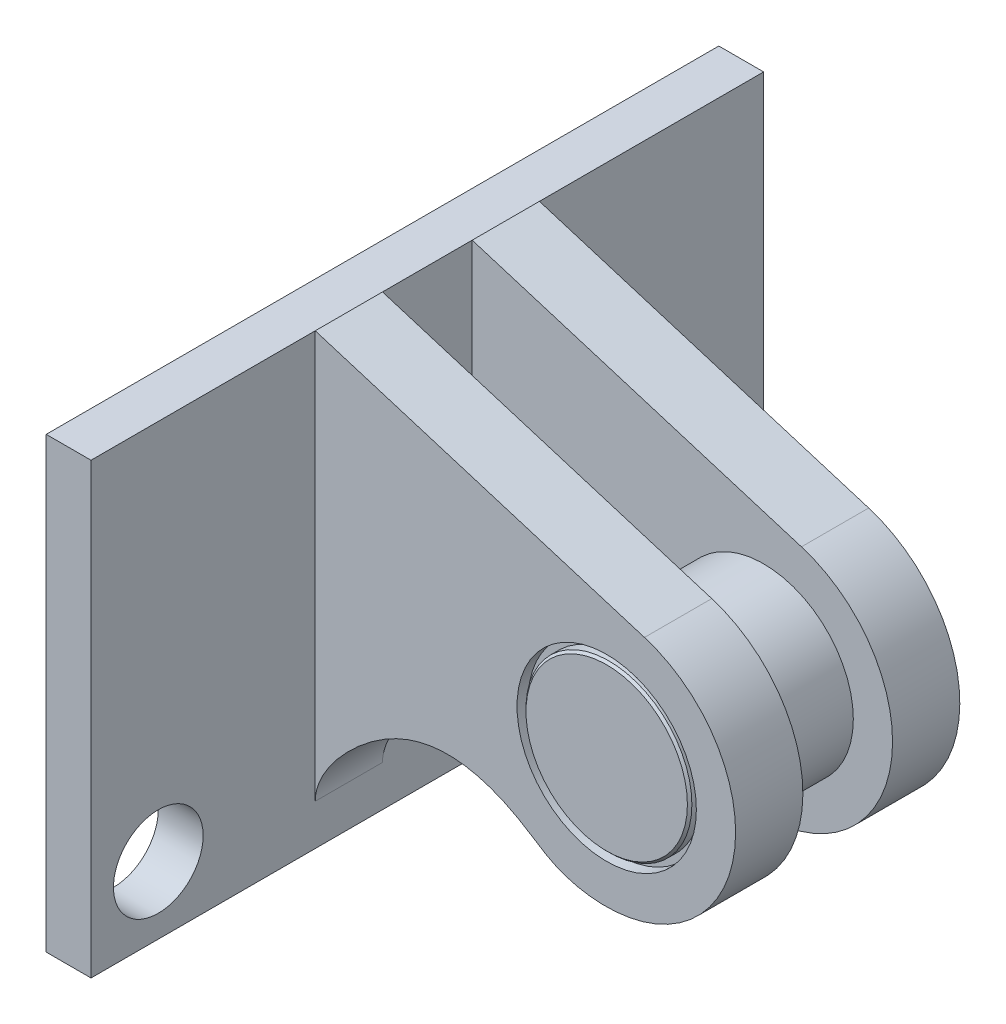
SolidWorks part; units mm, degrees
ref_plane "Alzado" through (0, 0, 0) normal (0, 0, 1) x (1, 0, 0)
ref_plane "Planta" through (0, 0, 0) normal (0, 1, 0) x (1, 0, 0)
ref_plane "Vista lateral" through (0, 0, 0) normal (1, 0, 0) x (0, 0, -1)
sketch "Croquis1" plane through (0, 0, 0) normal (0, 0, 1) x (1, 0, 0)
sketch_block_instance "chumacera-2"
sketch_block "chumacera" parameters "D1"=8, "D2"=15, "D3"=7
ref_plane "Plano1" through (4.6598, 0, 0) normal (1, 0, 0) x (0, 0, -1)
sketch "Croquis2" plane through (4.6598, 0, 0) normal (1, 0, 0) x (0, 0, -1)
  line L1 (-15, -22.0058) -> (15, -22.0058)
  line L2 (-15, -22.0058) -> (-15, -2.0058)
  line L3 (-15, -2.0058) -> (15, -2.0058)
  line L4 (15, -22.0058) -> (15, -2.0058)
  line L5 (-15, -22.0058) -> (15, -2.0058) construction
  line L6 (-15, -2.0058) -> (15, -22.0058) construction
  point P0 (0, -12.0058)
  point P2 (0, -12.0058)
  dimension "D1" = 30
  dimension "D2" = 20
extrude "Saliente-Extruir1" add sketch "Croquis2" along normal blind 2
ref_plane "Plano2" through (0, 0, 2) normal (0, 0, 1) x (1, 0, 0)
sketch "Croquis3" plane through (0, 0, 2) normal (0, 0, 1) x (1, 0, 0)
  line L0 (4.6598, -12.0058) -> (19.6598, -12.0058) construction
  line L1 (4.6598, -12.0058) -> (19.6598, -12.0058) construction
  line L2 (6.6598, -2.0058) -> (6.6598, -22.0058) construction
  line L3 (6.6598, -2.0058) -> (6.6598, -20.1789)
  line L4 (6.6598, -2.0058) -> (21.3453, -6.5084)
  line L5 (6.6598, -20.1789) -> (20.6748, -17.6655) construction
  circle A0 centre (19.6598, -12.0058) radius 4 construction
  circle A1 centre (19.6598, -12.0058) radius 4
  circle A2 centre (19.6598, -12.0058) radius 5.75 construction
  arc A3 (20.6748, -17.6655) -> (21.3453, -6.5084) centre (19.6598, -12.0058) ccw
  spline S0 degree 3 poles (20.6748, -17.6655) (19.5349, -17.8699) (17.7927, -17.715) (14.4778, -15.3673) (10.5194, -14.5252) (6.6598, -19.0081) (6.6598, -20.1789) knots 0 0 0 0 0.229346 0.306026 0.766799 1 1 1 1
  dimension "D1" = 5.75
extrude "Saliente-Extruir2" add sketch "Croquis3" along normal blind 3 contours L5 A3 L4 L3 A1 region at (13.6485, -10.3204, 2)
mirror "Simetría1" about plane through (0, 0, 0) normal (0, 0, 1) of "Saliente-Extruir2"
sketch "Croquis4" plane through (6.6598, 0, 0) normal (1, 0, 0) x (0, 0, -1)
  line L0 (-15, -22.0058) -> (15, -22.0058) construction
  line L1 (-15, -2.0058) -> (-15, -22.0058) construction
  circle A0 centre (-12, -19.0058) radius 2
  dimension "D1" = 3
  dimension "D3" = 4
  dimension "D2" = 3
extrude "Cortar-Extruir1" cut sketch "Croquis4" against normal up to next
sketch "Croquis5" plane through (0, 0, 5) normal (0, 0, 1) x (1, 0, 0)
  circle A0 centre (19.6598, -12.0058) radius 4 construction
  circle A1 centre (19.6598, -12.0058) radius 4
extrude "Saliente-Extruir3" add sketch "Croquis5" against normal up to surface (10 mm away) separate body up to face at (16.6841, -11.3414, -5)
sketch "Croquis6" plane through (0, 0, 5) normal (0, 0, 1) x (1, 0, 0)
  circle A0 centre (19.6598, -12.0058) radius 4 construction
  circle A1 centre (19.6598, -12.0058) radius 4
  circle A2 centre (19.6598, -12.0058) radius 3.7
  dimension "D1" = 0.3
extrude "Cortar-Extruir2" cut sketch "Croquis6" against normal blind 0.5
chamfer "Chaflán1" distance 0.1 angle 45 1 edges at (23.3598, -12.0058, 5)
mirror "Simetría3" about plane through (0, 0, 0) normal (0, 0, 1) of "Cortar-Extruir2"
chamfer "Chaflán2" distance 0.1 angle 45 1 edges at (23.3598, -12.0058, -5)
